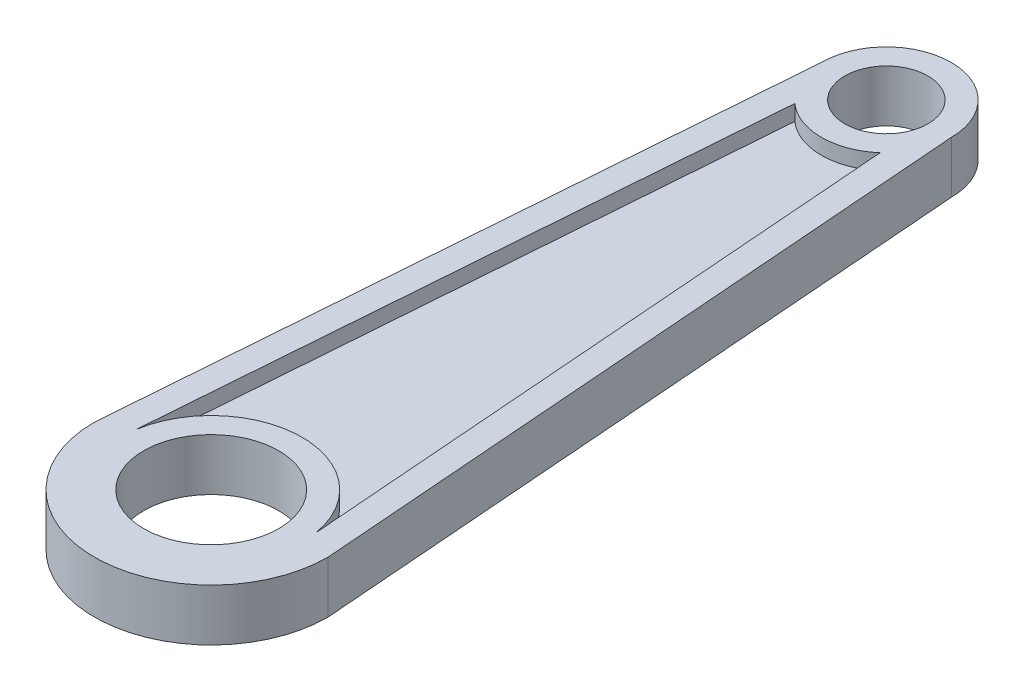
SolidWorks part; units mm, degrees
note: The reader was unsure of these and kept them because the rebuilt part matched: shared geometry of "Sketch2<3>".
ref_plane "Front Plane" through (0, 0, 0) normal (0, 0, 1) x (1, 0, 0)
ref_plane "Top Plane" through (0, 0, 0) normal (0, 1, 0) x (1, 0, 0)
ref_plane "Right Plane" through (0, 0, 0) normal (1, 0, 0) x (0, 0, -1)
sketch "Sketch1" plane through (0, 0, 0) normal (0, 1, 0) x (1, 0, 0)
  line L0 (0, 0) -> (0, 130) construction
  line L1 (-22.5, 0) -> (-12.5, 130)
  line L2 (22.5, 0) -> (12.5, 130)
  circle A0 centre (0, 0) radius 13
  circle A1 centre (0, 0) radius 22.5
  circle A2 centre (0, 130) radius 8
  circle A3 centre (0, 130) radius 12.5
  dimension "D1" = 26
  dimension "D2" = 45
  dimension "D3" = 25
  dimension "D4" = 16
  dimension "D5" = 130
extrude "Boss-Extrude1" add sketch "Sketch1" along normal mid plane 10
sketch "Sketch2" plane through (0, 0, 0) normal (0, 1, 0) x (1, 0, 0)
  line L0 (-8.2103, 120.5744) -> (-17.2657, 2.8542)
  line L1 (17.2657, 2.8542) -> (8.2103, 120.5744)
  line L2 (-12.5, 130) -> (-22.5, 0)
  line L3 (22.5, 0) -> (12.5, 130)
  line L4 (-12.5, 130) -> (-22.5, 0) construction
  line L5 (22.5, 0) -> (12.5, 130) construction
  line L6 (-7.4981, 129.8323) -> (-17.4991, -0.18) construction
  line L7 (17.4991, -0.18) -> (7.4981, 129.8323) construction
  arc A2 (12.5, 130) -> (-12.5, 130) centre (0, 130) ccw
  arc A3 (-22.5, 0) -> (22.5, 0) centre (0, 0) ccw
  arc A4 (12.5, 130) -> (-12.5, 130) centre (0, 130) ccw construction
  arc A5 (-22.5, 0) -> (22.5, 0) centre (0, 0) ccw construction
  arc A6 (-8.2103, 120.5744) -> (8.2103, 120.5744) centre (0, 130) ccw
  arc A7 (7.4981, 129.8323) -> (-7.4981, 129.8323) centre (0, 130) ccw construction
  arc A8 (-17.2657, 2.8542) -> (17.2657, 2.8542) centre (0, 0) cw
  arc A9 (-17.4991, -0.18) -> (17.4991, -0.18) centre (0, 0) ccw construction
  point P15 (0, 0)
  point P17 (0, 0)
  dimension "D3" = 12.5
  dimension "D1" = 0
  dimension "D2" = 5
extrude "Cut-Extrude1" cut sketch "Sketch2" along normal blind 3 from surface
extrude "Cut-Extrude2" cut sketch "Sketch2<3>" against normal blind 3 from surface at 5
sketch "Sketch2<3>" plane through (0, 0, 0) normal (0, 1, 0) x (1, 0, 0) same geometry as "Sketch2"
